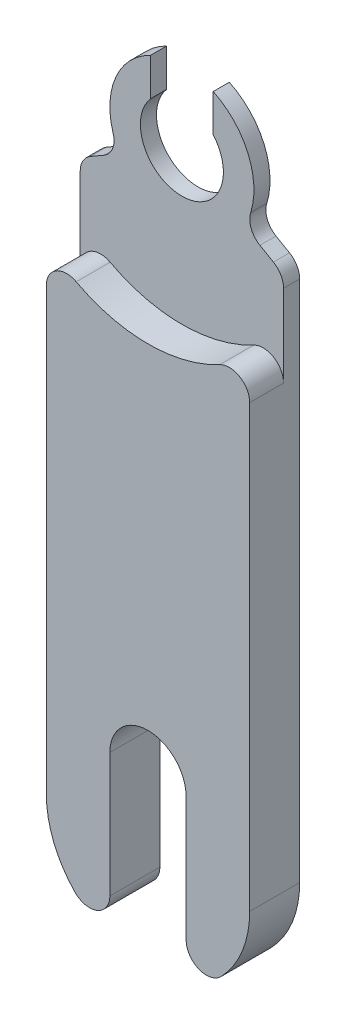
SolidWorks part; units mm, degrees
ref_plane "Front" through (0, 0, 0) normal (0, 0, 1) x (1, 0, 0)
ref_plane "Top" through (0, 0, 0) normal (0, 1, 0) x (1, 0, 0)
ref_plane "Right" through (0, 0, 0) normal (1, 0, 0) x (0, 0, -1)
sketch "Sketch3" plane through (0, 0, 0) normal (0, 0, 1) x (1, 0, 0)
  line L0 (0, 0) -> (0, -35) construction
  line L1 (6, 0) -> (6, -35)
  line L2 (-6, 0) -> (-6, -35)
  circle A0 centre (0, 0) radius 2.45
  arc A2 (6, 0) -> (-6, 0) centre (0, 0) ccw
  arc A3 (-6, -35) -> (6, -35) centre (0, -35) ccw
  dimension "D1" = 6
  dimension "D2" = 4.9
  dimension "D4" = 6
  dimension "D3" = 35
extrude "Boss-Extrude1" add sketch "Sketch3" along normal blind 0.95
sketch "Sketch4" plane through (0, 0, 0.95) normal (0, 0, 1) x (1, 0, 0)
  line L1 (-1.85, 0) -> (1.85, 0)
  line L2 (-1.85, 0) -> (-1.85, 6)
  line L3 (-1.85, 6) -> (1.85, 6)
  line L4 (1.85, 0) -> (1.85, 6)
  line L5 (0, 6) -> (0, 0) construction
  line L6 (-1.85, 3) -> (1.85, 3) construction
  arc A0 (6, 0) -> (-6, 0) centre (0, 0) ccw construction
  point P116 (0, 3)
  dimension "D1" = 3.7
extrude "Cut-Extrude1" cut sketch "Sketch4" against normal blind 1
sketch "Sketch5" plane through (0, 0, 0.95) normal (0, 0, 1) x (1, 0, 0)
  line L0 (-6, 0) -> (-6, -35) construction
  line L1 (6, -35) -> (6, 0) construction
  line L2 (-6, -6.7082) -> (0, 0) construction
  line L3 (0, 0) -> (6, -6.7082) construction
  line L4 (-1.85, 1.6062) -> (-1.85, 5.7077)
  line L5 (-6, 0) -> (-6, -35)
  line L6 (6, -35) -> (6, 0)
  line L7 (1.85, 5.7077) -> (1.85, 1.6062)
  line L9 (-6, -6.7082) -> (-6, -35)
  line L10 (6, -35) -> (6, -6.7082)
  arc A0 (-6, -6.7082) -> (6, -6.7082) centre (0, 0) ccw
  arc A4 (-1.85, 5.7077) -> (-6, 0) centre (0, 0) ccw
  arc A5 (-6, -35) -> (6, -35) centre (0, -35) ccw
  arc A6 (6, 0) -> (1.85, 5.7077) centre (0, 0) ccw
  arc A7 (-1.85, 1.6062) -> (1.85, 1.6062) centre (0, 0) ccw
  arc A9 (-6, -35) -> (6, -35) centre (0, -35) ccw
  dimension "D2" = 9
  dimension "D1" = 0
extrude "Boss-Extrude2" add sketch "Sketch5" along normal blind 2
sketch "Sketch6" plane through (0, 0, 2.95) normal (0, 0, 1) x (1, 0, 0)
  line L0 (0, -31) -> (0, -41) construction
  line L1 (2.25, -31) -> (2.25, -41)
  line L2 (-2.25, -31) -> (-2.25, -41)
  arc A0 (2.25, -31) -> (-2.25, -31) centre (0, -31) ccw
  arc A1 (-2.25, -41) -> (2.25, -41) centre (0, -41) ccw
  arc A2 (-6, -35) -> (6, -35) centre (0, -35) ccw construction
  point P4 (0, -36)
  dimension "D1" = 4.5
  dimension "D2" = 10
extrude "Cut-Extrude2" cut sketch "Sketch6" against normal through all
sketch "Sketch7" plane through (0, 0, 0.95) normal (0, 0, 1) x (1, 0, 0)
  line L0 (-6, -3.4641) -> (-3.6806, -2.125)
  line L1 (0, 0) -> (0, -4.25) construction
  line L2 (6, -3.4641) -> (3.6806, -2.125)
  line L3 (6, -6.7082) -> (6, 0) construction
  line L4 (6, -6.7082) -> (6, 0)
  line L5 (1.85, 5.7077) -> (1.85, 1.6062)
  line L6 (-1.85, 1.6062) -> (-1.85, 5.7077)
  line L7 (-6, 0) -> (-6, -6.7082)
  line L8 (6, -3.4641) -> (6, 0)
  line L9 (1.85, 5.7077) -> (1.85, 1.6062)
  line L10 (-1.85, 1.6062) -> (-1.85, 5.7077)
  line L11 (-6, 0) -> (-6, -3.4641)
  circle A0 centre (0, 0) radius 4.25
  arc A8 (-6, -6.7082) -> (6, -6.7082) centre (0, 0) ccw
  arc A10 (6, 0) -> (1.85, 5.7077) centre (0, 0) ccw
  arc A11 (-1.85, 1.6062) -> (1.85, 1.6062) centre (0, 0) ccw
  arc A12 (-1.85, 5.7077) -> (-6, 0) centre (0, 0) ccw
  arc A16 (6, 0) -> (1.85, 5.7077) centre (0, 0) ccw
  arc A17 (-1.85, 1.6062) -> (1.85, 1.6062) centre (0, 0) ccw
  arc A18 (-1.85, 5.7077) -> (-6, 0) centre (0, 0) ccw
  point P4 (6, -5.5848)
  line M13 (6, -6.7082) -> (6, 0)
  arc M14 (6, 0) -> (1.85, 5.7077) centre (0, 0) ccw
  line M15 (1.85, 5.7077) -> (1.85, 1.6062)
  arc M18 (-1.85, 5.7077) -> (-6, 0) centre (0, 0) ccw
  line M19 (-6, 0) -> (-6, -6.7082)
  dimension "D2" = 1.8
  dimension "D3" = 120
  dimension "D1" = 0
extrude "Cut-Extrude3" cut sketch "Sketch7" against normal through all contours A0 L10 L0 M18 M19 | A0 L2 M13 M14 M15 region at (-4.3855, 1.2927, 0.95) region at (4.3855, 1.2927, 0.95)
fillet "Fillet1" radius 1.2 8 edges at (2.25, -40.5621, 1.475) (-2.25, -40.5621, 1.475) (-6, -6.7082, 1.95) (6, -6.7082, 1.95) (-3.6806, -2.125, 0.475) (3.6806, -2.125, 0.475) (6, -3.4641, 0.475) (-6, -3.4641, 0.475) tangent propagation no
